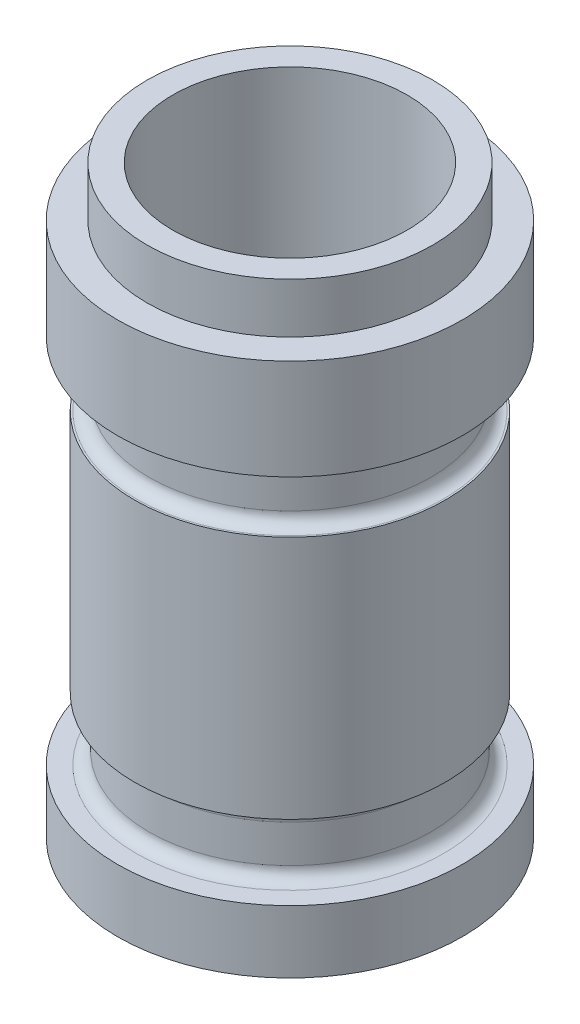
SolidWorks part; units mm, degrees
material "Copper"
ref_plane "Front Plane" through (0, 0, 0) normal (0, 0, 1) x (1, 0, 0)
ref_plane "Top Plane" through (0, 0, 0) normal (0, 1, 0) x (1, 0, 0)
ref_plane "Right Plane" through (0, 0, 0) normal (1, 0, 0) x (0, 0, -1)
sketch "Sketch1" plane through (0, 0, 0) normal (0, 0, 1) x (1, 0, 0)
  line L0 (0, 236.22) -> (0, 0) construction
  line L1 (0, 0) -> (0, 0.5)
  line L2 (0, 0) -> (2.75, 0)
  line L3 (2.75, 0) -> (2.75, 1)
  line L4 (2.75, 1) -> (2.45, 1)
  line L5 (0, 0.5) -> (1.37, 0.9879)
  line L6 (1.37, 0.9879) -> (1.87, 0.9879)
  line L7 (1.87, 0.9879) -> (1.87, 9.324)
  line L8 (2.25, 1.2) -> (2.25, 1.8)
  line L9 (2.45, 2) -> (2.479, 2)
  line L10 (2.479, 2) -> (2.479, 5.9)
  line L11 (2.479, 5.9) -> (2.45, 5.9)
  line L12 (2.25, 6.1) -> (2.25, 6.724)
  line L13 (2.45, 6.924) -> (2.75, 6.924)
  line L14 (2.75, 6.924) -> (2.75, 8.524)
  line L15 (2.75, 8.524) -> (2.28, 8.524)
  line L16 (2.28, 8.524) -> (2.28, 9.324)
  line L17 (2.28, 9.324) -> (1.87, 9.324)
  arc A0 (2.45, 1) -> (2.25, 1.2) centre (2.45, 1.2) cw
  arc A1 (2.45, 2) -> (2.25, 1.8) centre (2.45, 1.8) ccw
  arc A2 (2.45, 5.9) -> (2.25, 6.1) centre (2.45, 6.1) cw
  arc A3 (2.25, 6.724) -> (2.45, 6.924) centre (2.45, 6.724) cw
  point P13 (2.25, 1)
  point P17 (2.25, 2)
  dimension "D7" = 1
  dimension "D9" = 0.2
  dimension "D12" = 0.2
  dimension "D14" = 1.6
  dimension "D8" = 0.2
  dimension "D1" = 0.5
  dimension "D2" = 2.75
  dimension "D3" = 1
  dimension "D4" = 0.3
  dimension "D5" = 9.324
  dimension "D6" = 0.5
  dimension "D10" = 0.029
  dimension "D11" = 3.9
  dimension "D15" = 0.47
  dimension "D16" = 0.41
  dimension "D17" = 0.8
  dimension "D18" = 160.399
revolve "Revolve1" add sketch "Sketch1" angle 360 about L0
cosmetic thread "Cosmetic Thread1" parameters "D2"=4
